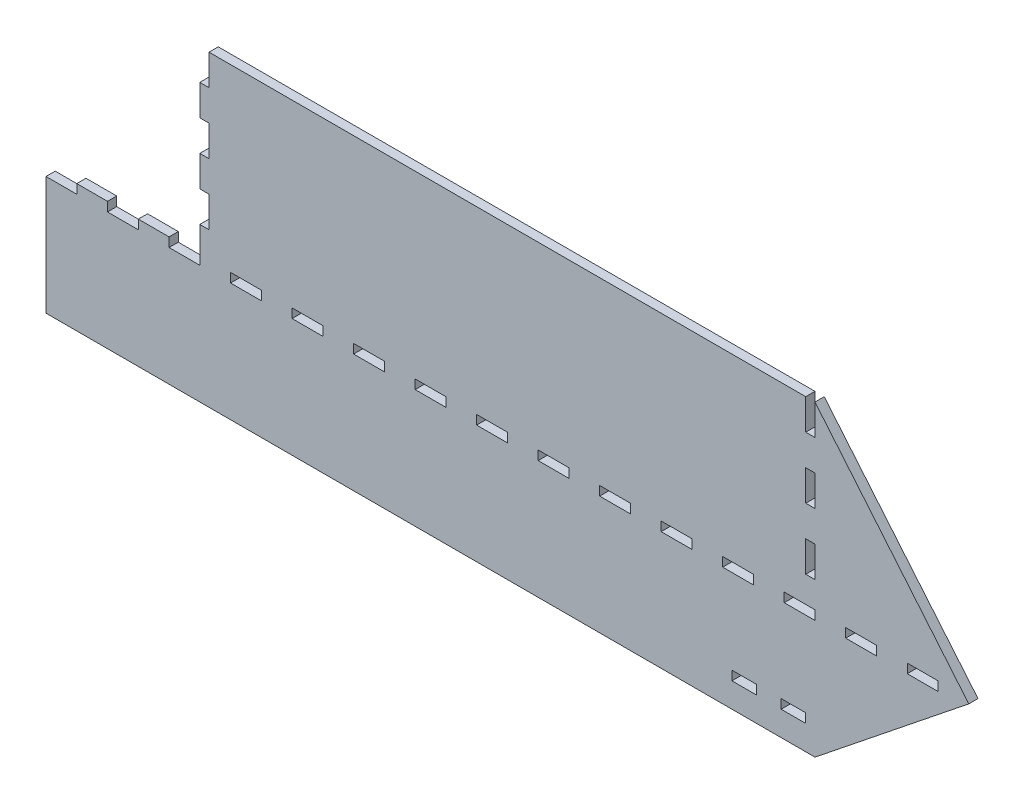
SolidWorks part; units mm, degrees
ref_plane "Front Plane" through (0, 0, 0) normal (0, 0, 1) x (1, 0, 0)
ref_plane "Top Plane" through (0, 0, 0) normal (0, 1, 0) x (1, 0, 0)
ref_plane "Right Plane" through (0, 0, 0) normal (1, 0, 0) x (0, 0, -1)
sketch "Sketch1" plane through (0, 0, 0) normal (0, 0, 1) x (1, 0, 0)
  line L0 (-113.8765, -92.2284) -> (-113.8765, -52.2284)
  line L1 (-113.8765, -52.2284) -> (-113.8765, -50.7284)
  line L2 (-103.8765, -50.7284) -> (-93.8765, -50.7284)
  line L3 (-60.8765, 7.7716) -> (133.1235, 7.7716)
  line L4 (136.1235, 7.7716) -> (186.1235, -52.2284)
  line L5 (186.1235, -52.2284) -> (136.1235, -92.2284)
  line L6 (136.1235, -92.2284) -> (-113.8765, -92.2284)
  line L7 (186.1235, -52.2284) -> (-63.8765, -52.2284) construction
  line L8 (-63.8765, -50.7284) -> (-63.8765, -42.2284)
  line L9 (156.1235, -50.7284) -> (146.1235, -50.7284)
  line L10 (176.1235, -50.7284) -> (166.1235, -50.7284)
  line L11 (176.1235, -50.7284) -> (176.1235, -53.7284)
  line L12 (176.1235, -53.7284) -> (166.1235, -53.7284)
  line L13 (166.1235, -50.7284) -> (166.1235, -53.7284)
  line L14 (176.1235, -50.7284) -> (166.1235, -53.7284) construction
  line L15 (176.1235, -53.7284) -> (166.1235, -50.7284) construction
  line L16 (156.1235, -50.7284) -> (156.1235, -53.7284)
  line L17 (156.1235, -53.7284) -> (146.1235, -53.7284)
  line L18 (146.1235, -50.7284) -> (146.1235, -53.7284)
  line L19 (156.1235, -50.7284) -> (146.1235, -53.7284) construction
  line L20 (156.1235, -53.7284) -> (146.1235, -50.7284) construction
  line L21 (136.1235, -50.7284) -> (126.1235, -50.7284)
  line L22 (136.1235, -50.7284) -> (136.1235, -53.7284)
  line L23 (136.1235, -53.7284) -> (126.1235, -53.7284)
  line L24 (126.1235, -50.7284) -> (126.1235, -53.7284)
  line L25 (136.1235, -50.7284) -> (126.1235, -53.7284) construction
  line L26 (136.1235, -53.7284) -> (126.1235, -50.7284) construction
  line L27 (116.1235, -50.7284) -> (106.1235, -50.7284)
  line L28 (116.1235, -50.7284) -> (116.1235, -53.7284)
  line L29 (116.1235, -53.7284) -> (106.1235, -53.7284)
  line L30 (106.1235, -50.7284) -> (106.1235, -53.7284)
  line L31 (116.1235, -50.7284) -> (106.1235, -53.7284) construction
  line L32 (116.1235, -53.7284) -> (106.1235, -50.7284) construction
  line L33 (96.1235, -50.7284) -> (86.1235, -50.7284)
  line L34 (96.1235, -50.7284) -> (96.1235, -53.7284)
  line L35 (96.1235, -53.7284) -> (86.1235, -53.7284)
  line L36 (86.1235, -50.7284) -> (86.1235, -53.7284)
  line L37 (96.1235, -50.7284) -> (86.1235, -53.7284) construction
  line L38 (96.1235, -53.7284) -> (86.1235, -50.7284) construction
  line L39 (76.1235, -50.7284) -> (66.1235, -50.7284)
  line L40 (76.1235, -50.7284) -> (76.1235, -53.7284)
  line L41 (76.1235, -53.7284) -> (66.1235, -53.7284)
  line L42 (66.1235, -50.7284) -> (66.1235, -53.7284)
  line L43 (76.1235, -50.7284) -> (66.1235, -53.7284) construction
  line L44 (76.1235, -53.7284) -> (66.1235, -50.7284) construction
  line L45 (56.1235, -50.7284) -> (46.1235, -50.7284)
  line L46 (56.1235, -50.7284) -> (56.1235, -53.7284)
  line L47 (56.1235, -53.7284) -> (46.1235, -53.7284)
  line L48 (46.1235, -50.7284) -> (46.1235, -53.7284)
  line L49 (56.1235, -50.7284) -> (46.1235, -53.7284) construction
  line L50 (56.1235, -53.7284) -> (46.1235, -50.7284) construction
  line L51 (36.1235, -50.7284) -> (26.1235, -50.7284)
  line L52 (36.1235, -50.7284) -> (36.1235, -53.7284)
  line L53 (36.1235, -53.7284) -> (26.1235, -53.7284)
  line L54 (26.1235, -50.7284) -> (26.1235, -53.7284)
  line L55 (36.1235, -50.7284) -> (26.1235, -53.7284) construction
  line L56 (36.1235, -53.7284) -> (26.1235, -50.7284) construction
  line L57 (16.1235, -50.7284) -> (6.1235, -50.7284)
  line L58 (16.1235, -50.7284) -> (16.1235, -53.7284)
  line L59 (16.1235, -53.7284) -> (6.1235, -53.7284)
  line L60 (6.1235, -50.7284) -> (6.1235, -53.7284)
  line L61 (16.1235, -50.7284) -> (6.1235, -53.7284) construction
  line L62 (16.1235, -53.7284) -> (6.1235, -50.7284) construction
  line L63 (-3.8765, -50.7284) -> (-13.8765, -50.7284)
  line L64 (-3.8765, -50.7284) -> (-3.8765, -53.7284)
  line L65 (-3.8765, -53.7284) -> (-13.8765, -53.7284)
  line L66 (-13.8765, -50.7284) -> (-13.8765, -53.7284)
  line L67 (-3.8765, -50.7284) -> (-13.8765, -53.7284) construction
  line L68 (-3.8765, -53.7284) -> (-13.8765, -50.7284) construction
  line L69 (-23.8765, -50.7284) -> (-33.8765, -50.7284)
  line L70 (-23.8765, -50.7284) -> (-23.8765, -53.7284)
  line L71 (-23.8765, -53.7284) -> (-33.8765, -53.7284)
  line L72 (-33.8765, -50.7284) -> (-33.8765, -53.7284)
  line L73 (-23.8765, -50.7284) -> (-33.8765, -53.7284) construction
  line L74 (-23.8765, -53.7284) -> (-33.8765, -50.7284) construction
  line L75 (-43.8765, -50.7284) -> (-53.8765, -50.7284)
  line L76 (-43.8765, -50.7284) -> (-43.8765, -53.7284)
  line L77 (-43.8765, -53.7284) -> (-53.8765, -53.7284)
  line L78 (-53.8765, -50.7284) -> (-53.8765, -53.7284)
  line L79 (-43.8765, -50.7284) -> (-53.8765, -53.7284) construction
  line L80 (-43.8765, -53.7284) -> (-53.8765, -50.7284) construction
  line L81 (-83.8765, -50.7284) -> (-73.8765, -50.7284)
  line L82 (-63.8765, -50.7284) -> (-63.8765, -53.7284)
  line L83 (-63.8765, -53.7284) -> (-73.8765, -53.7284)
  line L84 (-73.8765, -50.7284) -> (-73.8765, -53.7284)
  line L85 (-63.8765, -50.7284) -> (-73.8765, -53.7284) construction
  line L86 (-63.8765, -53.7284) -> (-73.8765, -50.7284) construction
  line L87 (136.1235, -22.2284) -> (133.1235, -22.2284)
  line L88 (-83.8765, -50.7284) -> (-83.8765, -53.7284)
  line L89 (-83.8765, -53.7284) -> (-93.8765, -53.7284)
  line L90 (-93.8765, -50.7284) -> (-93.8765, -53.7284)
  line L91 (-83.8765, -50.7284) -> (-93.8765, -53.7284) construction
  line L92 (-83.8765, -53.7284) -> (-93.8765, -50.7284) construction
  line L93 (136.1235, -42.2284) -> (133.1235, -42.2284)
  line L94 (-103.8765, -50.7284) -> (-103.8765, -53.7284)
  line L95 (-103.8765, -53.7284) -> (-113.8765, -53.7284)
  line L96 (-113.8765, -50.7284) -> (-113.8765, -53.7284)
  line L97 (-103.8765, -50.7284) -> (-113.8765, -53.7284) construction
  line L98 (-103.8765, -53.7284) -> (-113.8765, -50.7284) construction
  line L99 (-63.8765, -50.7284) -> (-73.8765, -50.7284) [skipped]
  line L100 (-83.8765, -50.7284) -> (-93.8765, -50.7284) [skipped]
  line L101 (-103.8765, -50.7284) -> (-113.8765, -50.7284) [skipped]
  line L102 (136.1235, -42.2284) -> (136.1235, -32.2284)
  line L103 (136.1235, -32.2284) -> (133.1235, -32.2284)
  line L104 (133.1235, -42.2284) -> (133.1235, -32.2284)
  line L105 (136.1235, -22.2284) -> (136.1235, -12.2284)
  line L106 (136.1235, -12.2284) -> (133.1235, -12.2284)
  line L107 (133.1235, -22.2284) -> (133.1235, -12.2284)
  line L108 (136.1235, -2.2284) -> (133.1235, -2.2284)
  line L109 (136.1235, -2.2284) -> (136.1235, 7.7716)
  line L110 (-63.8765, -22.2284) -> (-60.8765, -22.2284)
  line L111 (133.1235, -2.2284) -> (133.1235, 7.7716)
  line L112 (136.1235, 7.7716) -> (133.1235, 7.7716) [skipped]
  line L113 (-63.8765, -42.2284) -> (-60.8765, -42.2284)
  line L114 (117.1235, -84.2284) -> (109.1235, -84.2284)
  line L115 (-63.8765, -32.2284) -> (-60.8765, -32.2284)
  line L116 (-60.8765, -42.2284) -> (-60.8765, -32.2284)
  line L117 (-63.8765, -32.2284) -> (-63.8765, -22.2284)
  line L118 (-63.8765, -12.2284) -> (-60.8765, -12.2284)
  line L119 (-60.8765, -22.2284) -> (-60.8765, -12.2284)
  line L120 (-63.8765, -2.2284) -> (-60.8765, -2.2284)
  line L121 (-63.8765, -12.2284) -> (-63.8765, -2.2284)
  line L122 (133.1235, -84.2284) -> (125.1235, -84.2284)
  line L123 (-60.8765, -2.2284) -> (-60.8765, 7.7716)
  line L124 (-63.8765, 7.7716) -> (-60.8765, 7.7716) [skipped]
  line L125 (133.1235, -84.2284) -> (133.1235, -81.2284)
  line L126 (133.1235, -81.2284) -> (125.1235, -81.2284)
  line L127 (125.1235, -84.2284) -> (125.1235, -81.2284)
  line L128 (117.1235, -84.2284) -> (117.1235, -81.2284)
  line L129 (117.1235, -81.2284) -> (109.1235, -81.2284)
  line L130 (109.1235, -84.2284) -> (109.1235, -81.2284)
  point P6 (171.1235, -52.2284)
  point P14 (151.1235, -52.2284)
  point P19 (131.1235, -52.2284)
  point P24 (111.1235, -52.2284)
  point P29 (91.1235, -52.2284)
  point P34 (71.1235, -52.2284)
  point P39 (51.1235, -52.2284)
  point P44 (31.1235, -52.2284)
  point P49 (11.1235, -52.2284)
  point P54 (-8.8765, -52.2284)
  point P59 (-28.8765, -52.2284)
  point P64 (-48.8765, -52.2284)
  point P70 (-68.8765, -52.2284)
  point P75 (-88.8765, -52.2284)
  point P80 (-108.8765, -52.2284)
  dimension "D1" = 100
  dimension "D2" = 40
  dimension "D3" = 300
  dimension "D4" = 50
  dimension "D5" = 50
  dimension "D6" = 10
  dimension "D7" = 10
  dimension "D8" = 3
  dimension "D10" = 8
  dimension "D11" = 1.5
  dimension "D13" = 10
  dimension "D14" = 3
  dimension "D15" = 10
  dimension "D17" = 10
  dimension "D18" = 10
  dimension "D19" = 3
  dimension "D21" = 8
  dimension "D22" = 2
  dimension "D23" = 3
  dimension "D24" = 39
  dimension "D25" = 3
  dimension "D9" = 12
  dimension "D12" = 4
  dimension "D16" = 3
  dimension "D20" = 3
extrude "Boss-Extrude1" add sketch "Sketch1" along normal blind 3 contours L94 L95 L0 L6 L5 L4 L3 L8 L82 L83 L84 L81 L88 L89 L90 L2 L13 L10 L11 L12 L18 L9 L16 L17 L24 L21 L22 L23 L30 L27 L28 L29 L36 L33 L34 L35 L42 L39 L40 L41 L48 L45 L46 L47 region at (37.3982, -45.0355, 0)
